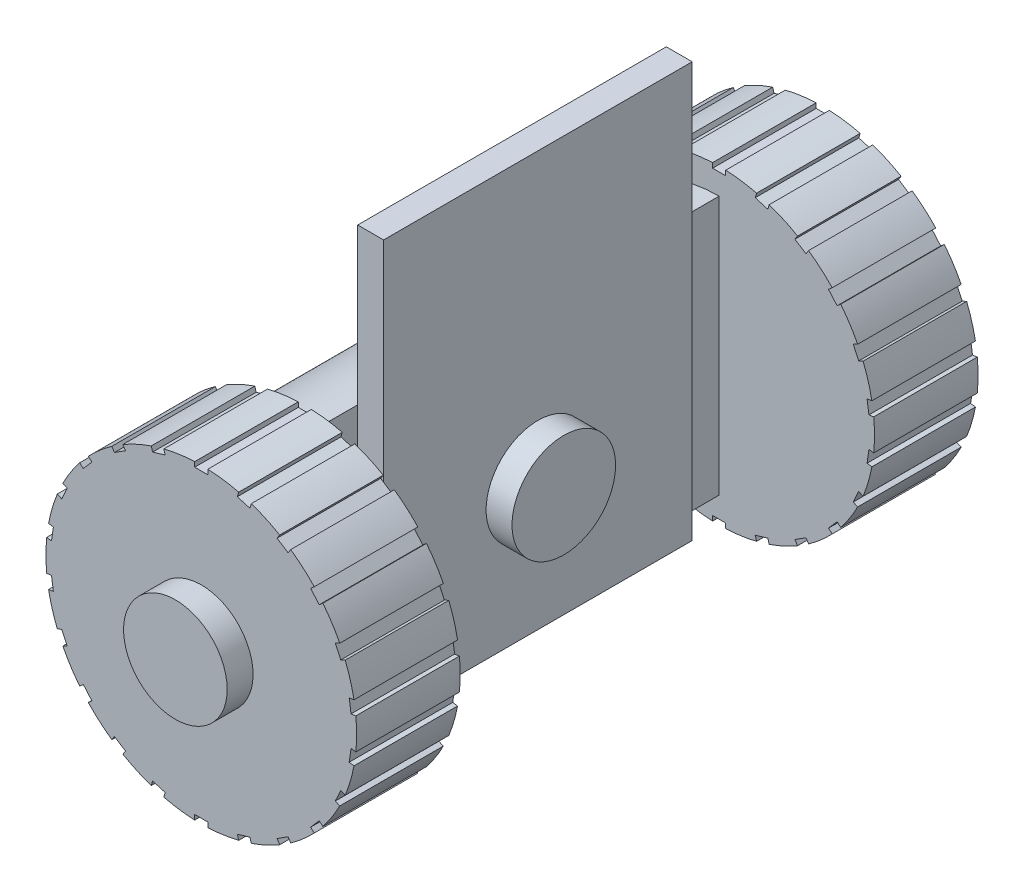
SolidWorks part; units mm, degrees
material "Malleable Cast Iron"
ref_plane "Front Plane" through (0, 0, 0) normal (0, 0, 1) x (1, 0, 0)
ref_plane "Top Plane" through (0, 0, 0) normal (0, 1, 0) x (1, 0, 0)
ref_plane "Right Plane" through (0, 0, 0) normal (1, 0, 0) x (0, 0, -1)
sketch "Sketch1" plane through (0, 0, 0) normal (0, 0, 1) x (1, 0, 0)
  circle A0 centre (0, 0) radius 30
  dimension "D1" = 60
extrude "Boss-Extrude1" add sketch "Sketch1" along normal blind 20
sketch "Sketch2" plane through (0, 0, 20) normal (0, 0, 1) x (1, 0, 0)
  circle A0 centre (0, 0) radius 10
  dimension "D1" = 20
extrude "Boss-Extrude2" add sketch "Sketch2" along normal blind 5
sketch "Sketch3" plane through (0, 0, 0) normal (0, 0, -1) x (-1, 0, 0)
  circle A0 centre (0, 0) radius 25
  dimension "D1" = 50
extrude "Boss-Extrude3" add sketch "Sketch3" along normal blind 80
ref_plane "Plane1" through (0, 0, -40) normal (0, 0, 1) x (1, 0, 0)
sketch "Sketch4" plane through (0, 0, 0) normal (0, 1, 0) x (1, 0, 0)
  line L1 (25, 80) -> (0, 80)
  line L2 (25, 80) -> (25, 0)
  line L3 (25, 0) -> (0, 0)
  line L4 (0, 80) -> (0, 0)
extrude "Cut-Extrude1" cut sketch "Sketch4" against normal blind 80 and the other way blind 80
sketch "Sketch5" plane through (0, 0, 20) normal (0, 0, 1) x (1, 0, 0)
  line L1 (-1.2662, 30.9641) -> (1.2662, 30.9641)
  line L2 (-1.2662, 30.9641) -> (-1.2662, 29.0359)
  line L3 (-1.2662, 29.0359) -> (1.2662, 29.0359)
  line L4 (1.2662, 30.9641) -> (1.2662, 29.0359)
  line L5 (-1.2662, 30.9641) -> (1.2662, 29.0359) construction
  line L6 (-1.2662, 29.0359) -> (1.2662, 30.9641) construction
  circle A0 centre (0, 0) radius 30 construction
  point P0 (0, 30)
extrude "Cut-Extrude2" cut sketch "Sketch5" against normal up to surface (20 mm away) up to face at (-12.5, 0, 0)
pattern_circular "CirPattern1" count 22 over 360 about axis through (0, 0, 25) along (0, 0, 1) of "Cut-Extrude2"
mirror "Mirror3" about plane through (0, 0, -40) normal (0, 0, 1) of "Boss-Extrude2", "CirPattern1", "Boss-Extrude1"
sketch "Sketch6" plane through (0, 0, 0) normal (1, 0, 0) x (0, 0, -1)
  line L0 (0, -25) -> (80, -25) construction
  line L1 (10.2044, -105.0738) -> (69.7956, -105.0738)
  line L2 (10.2044, -25) -> (10.2044, 55.0738)
  line L3 (10.2044, 55.0738) -> (69.7956, 55.0738)
  line L4 (69.7956, -25) -> (69.7956, 55.0738)
  line L5 (40, -25) -> (69.7956, 55.0738) construction
  line L6 (10.2044, 55.0738) -> (40, -25) construction
  line L7 (10.2044, -25) -> (69.7956, -25)
  point P0 (40, -25)
  line M5 (80, 25) -> (0, 25)
  line M7 (0, -25) -> (80, -25)
extrude "Boss-Extrude4" add sketch "Sketch6" along normal blind 5 contours L4 L3 L2 M5 | L4 L2 M7 M5 region at (0, 0, -40) region at (0, 40.0369, -40)
sketch "Sketch7" plane through (5, 0, 0) normal (1, 0, 0) x (0, 0, -1)
  line L1 (10.2044, -25) -> (69.7956, -25) construction
  circle A0 centre (40, 0) radius 10
  point P6 (40, -25)
  dimension "D1" = 20
extrude "Boss-Extrude5" add sketch "Sketch7" along normal blind 5
